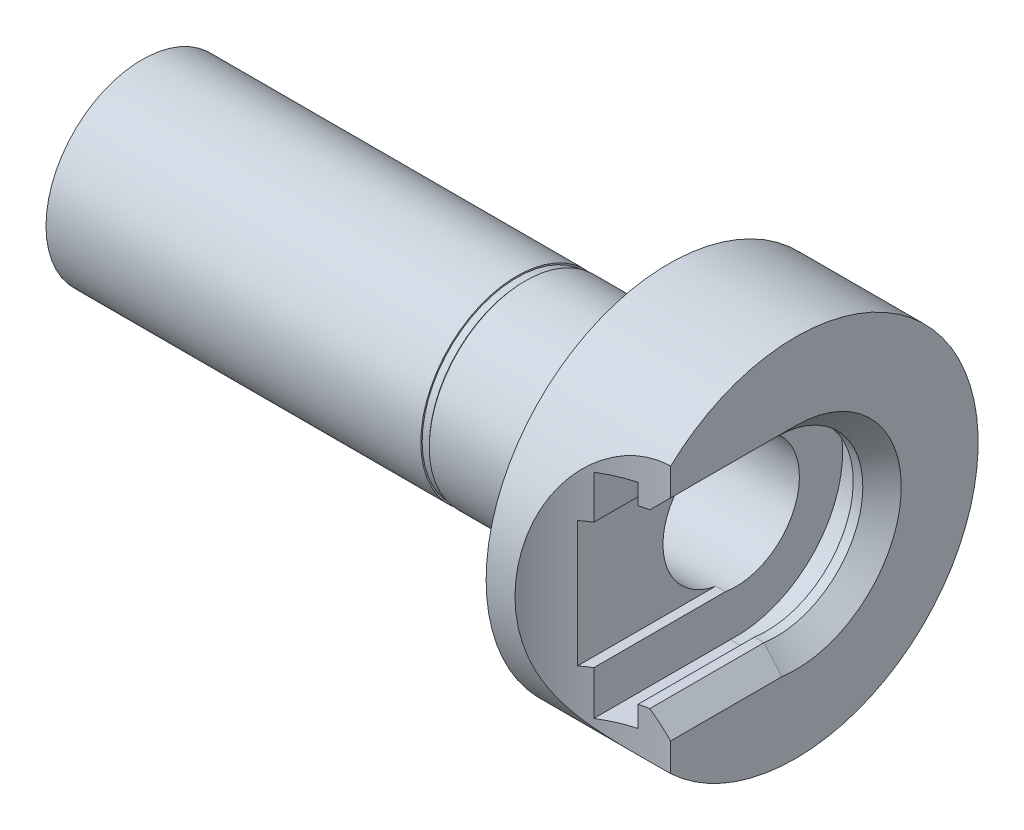
SolidWorks part; units mm, degrees
material "AISI 1020"
ref_plane "Plano superior" through (0, 0, 0) normal (0, 0, 1) x (1, 0, 0)
ref_plane "Plano frontal" through (0, 0, 0) normal (0, 1, 0) x (1, 0, 0)
ref_plane "Plano direito" through (0, 0, 0) normal (1, 0, 0) x (0, 0, -1)
sketch "Esboço1" plane through (0, 0, 0) normal (0, 1, 0) x (1, 0, 0)
  line L0 (0, 0) -> (35, 0) construction
  line L1 (35.0155, 4.5) -> (35.0155, 9.5)
  line L2 (35.0155, 9.5) -> (28.4155, 9.5)
  line L3 (28.4155, 9.5) -> (28.4155, 5)
  line L4 (28.4155, 5) -> (20.7561, 5)
  line L5 (0.0155, 5) -> (0.0155, 3.3)
  line L6 (0.0155, 3.3) -> (31.9155, 3.3)
  line L7 (31.9155, 3.3) -> (31.9155, 5.55)
  line L8 (31.9155, 5.55) -> (33.5155, 5.55)
  line L9 (33.5155, 5.55) -> (33.5155, 4.5)
  line L10 (33.5155, 4.5) -> (35.0155, 4.5)
  line L13 (20.5155, 5) -> (20.5155, 4.9286)
  line L18 (20.5155, 4.9286) -> (20.7561, 4.9286)
  line L19 (20.7561, 4.9286) -> (20.7561, 5)
  line L20 (20.5155, 5) -> (0.0155, 5)
  point P3 (33.5155, 5.025)
  dimension "D1" = 5.55
  dimension "D2" = 5
  dimension "D3" = 6.6
  dimension "D4" = 3.5
  dimension "D5" = 1.6
  dimension "D6" = 4.5
  dimension "D7" = 0
  dimension "D8" = 3.3
  dimension "D9" = 35
  dimension "D10" = 20.5
  dimension "D12" = 9.5
revolve "Revolução1" add sketch "Esboço1" angle 360 about L0
cosmetic thread "Representação de rosca5" parameters "D1"=19.5, "D2"=8.344
chamfer "Chanfro3" distance 0.2 angle 45 1 edges at (20.7561, 0, 5)
sketch "Esboço3" plane through (31.9155, 0, 0) normal (1, 0, 0) x (0, 0, -1)
  line L0 (0, 6.9864) -> (0, -11.2896) construction
  line L2 (0, 5.5494) -> (-12.0828, 5.5494)
  line L3 (0, 5.5494) -> (0, -5.5425)
  line L4 (0, -5.5425) -> (-12.0828, -5.5425)
  line L5 (-12.0828, 5.5494) -> (-12.0828, -5.5425)
extrude "Corte-extrusão1" cut sketch "Esboço3" along normal blind 1.6
sketch "Esboço4" plane through (31.9155, 0, 0) normal (1, 0, 0) x (0, 0, -1)
  line L0 (0, 4.5) -> (0, -6.006) construction
  line L2 (0, 4.5) -> (-12.2024, 4.5)
  line L3 (0, 4.5) -> (0, -4.4532)
  line L4 (0, -4.4532) -> (-12.2024, -4.4532)
  line L5 (-12.2024, 4.5) -> (-12.2024, -4.4532)
extrude "Corte-extrusão2" cut sketch "Esboço4" along normal blind 4
sketch "Esboço5" plane through (31.9155, 0, 0) normal (1, 0, 0) x (0, 0, -1)
  line L0 (0, 3.5157) -> (0, -3.545) construction
  line L2 (0, 3.3) -> (-9.7121, 3.3)
  line L3 (0, 3.3) -> (0, -3.252)
  line L4 (0, -3.252) -> (-9.7121, -3.252)
  line L5 (-9.7121, 3.3) -> (-9.7121, -3.252)
  circle A0 centre (0, 0) radius 3.3 construction
sketch "Esboço11" plane through (0.0155, 0, 0) normal (-1, 0, 0) x (0, 0, 1)
  circle A0 centre (0, 0) radius 6.2415
extrude "Corte-extrusão5" cut sketch "Esboço11" against normal blind 1
extrude "Corte-extrusão3" cut sketch "Esboço5" against normal blind 0.5
sketch "Esboço6" plane through (0, 0, 0) normal (0, 1, 0) x (1, 0, 0)
  line L0 (28.4155, -9.5) -> (31.4155, -9.5) construction
  line L1 (35.0155, -8.3916) -> (35.0155, 9.5) construction
  line L4 (28.4155, 9.5) -> (35.0155, 9.5)
  line L5 (31.0155, -9.5) -> (28.2155, -9.5)
  line L6 (28.4155, 9.5) -> (28.4155, -9.5) construction
  line L7 (28.4155, 9.5) -> (35.0155, 9.5) construction
  line L8 (35.0155, -6.5) -> (28.676, -6.5) construction
  arc A0 (29.9155, -9.5) -> (35.0155, -6.5) centre (35.0155, -12.335) cw
  spline S0 degree 3 poles (29.9155, -9.5) (30.6319, -12.2774) (37.6403, -12.3024) (36.7656, -6.8513) (35.0155, -6.5) knots 0 0 0 0 0.632855 1 1 1 1
  dimension "D1" = 16
  dimension "D2" = 1.5
extrude "Corte-extrusão4" cut sketch "Esboço6" against normal through all both and the other way through all
chamfer "Chanfro6" distance 1 angle 45 3 edges at (35.0155, -4.4532, 3.5736) (35.0155, -0.3244, -4.4883) (35.0155, 4.5, 3.25)
